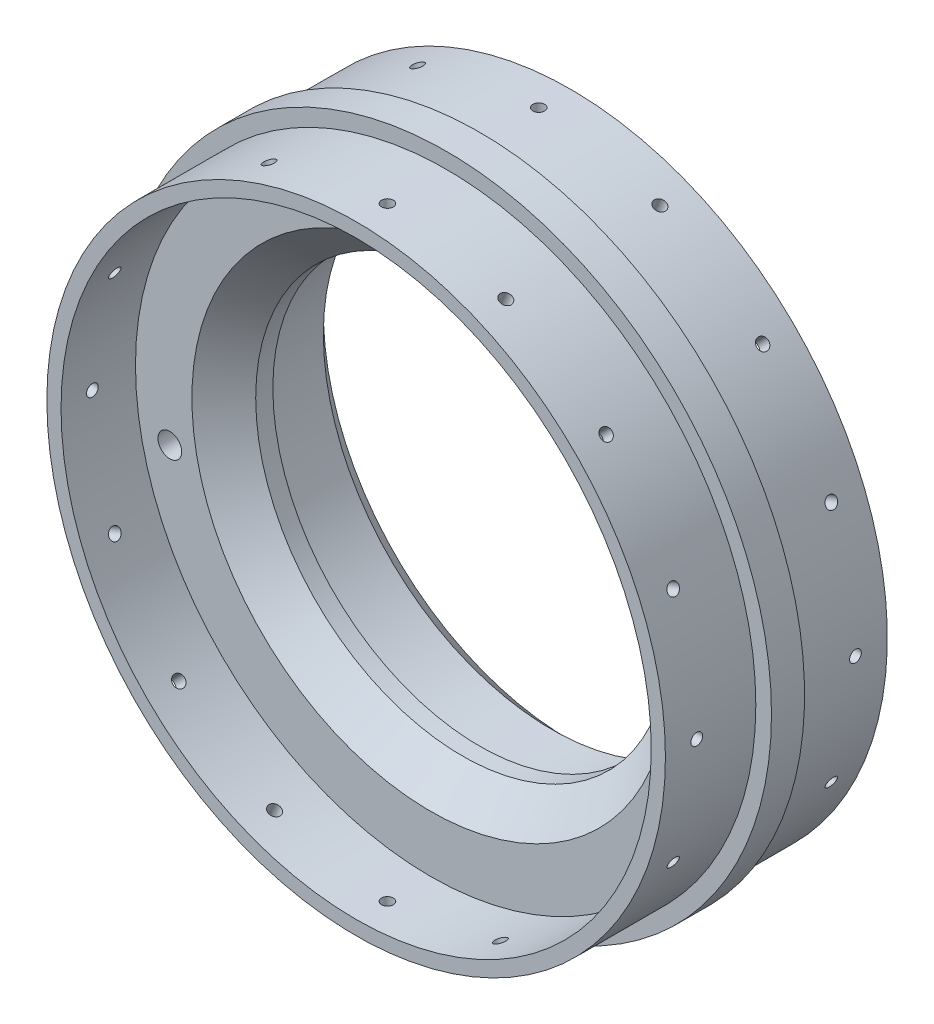
SolidWorks part; units mm, degrees
material "6061-T6 (SS)"
ref_plane "Front Plane" through (0, 0, 0) normal (0, 0, 1) x (1, 0, 0)
ref_plane "Top Plane" through (0, 0, 0) normal (0, 1, 0) x (1, 0, 0)
ref_plane "Right Plane" through (0, 0, 0) normal (1, 0, 0) x (0, 0, -1)
sketch "Sketch5" plane through (0, 0, 0) normal (0, 0, 1) x (1, 0, 0)
  circle A0 centre (0, 0) radius 69.85
extrude "Extrude1" add sketch "Sketch5" along normal blind 46.101
sketch "Sketch8" plane through (0, 0, 46.101) normal (0, 0, 1) x (1, 0, 0)
  circle A0 centre (0, 0) radius 44.45
extrude "Extrude4" cut sketch "Sketch8" against normal through all
sketch "Sketch6" plane through (0, 0, 46.101) normal (0, 0, 1) x (1, 0, 0)
  circle A0 centre (0, 0) radius 66.4845
extrude "Extrude2" cut sketch "Sketch6" against normal blind 19.431 flip side to cut
sketch "Sketch7" plane through (0, 0, 46.101) normal (0, 0, 1) x (1, 0, 0)
  circle A0 centre (0, 0) radius 63.4365
extrude "Extrude3" cut sketch "Sketch7" against normal blind 16.002
chamfer "Chamfer1" distance 6.858 distance2 6.858 1 edges at (44.45, 0, 30.099)
sketch "Sketch9" plane through (0, 0, 0) normal (0, 0, -1) x (-1, 0, 0)
  circle A0 centre (0, 0) radius 68.0847
extrude "Extrude5" cut sketch "Sketch9" against normal blind 19.558 flip side to cut
sketch "Sketch10" plane through (0, 0, 0) normal (0, 0, -1) x (-1, 0, 0)
  circle A0 centre (0, 0) radius 65.0367
  circle A1 centre (0, 0) radius 53.7845
extrude "Extrude6" cut sketch "Sketch10" against normal blind 9.525
sketch "Sketch11" plane through (0, 0, 0) normal (0, 0, -1) x (-1, 0, 0)
  circle A0 centre (0, 0) radius 49.0855
extrude "Extrude7" cut sketch "Sketch11" against normal blind 19.558
chamfer "Chamfer2" distance 4.064 angle 45 1 edges at (-49.0855, 0, 0)
ref_plane "Plane1" through (0, 0, 39.37) normal (0, 0, 1) x (1, 0, 0)
ref_plane "Plane2" through (0, 0, 6.858) normal (0, 0, -1) x (-1, 0, 0)
sketch "Sketch13" plane through (0, 0, 6.858) normal (0, 0, -1) x (-1, 0, 0)
  line L0 (0, 0) -> (0, 68.0847) construction
  circle A0 centre (0, 0) radius 68.0847 construction
ref_plane "Plane3" through (0, 68.0847, 6.858) normal (0, 1, 0) x (-1, 0, 0)
sketch "Sketch15" plane through (0, 0, 39.37) normal (0, 0, 1) x (1, 0, 0)
  line L0 (0, 0) -> (0, 66.4845) construction
  line L1 (0, 0) -> (0, 68.0847) construction
  circle A0 centre (0, 0) radius 66.4845 construction
ref_plane "Plane4" through (0, 66.4845, 39.37) normal (0, 1, 0) x (-1, 0, 0)
hole_wizard "#39 (0.0995) Diameter Hole2" positions "Sketch20" profile "Sketch19" hole size "#39" standard "Ansi Inch"
sketch "Sketch20" plane through (0, 68.0847, 6.858) normal (0, 1, 0) x (-1, 0, 0)
  point P1 (0, 0)
sketch "Sketch19" plane through (0, 68.0847, 6.858) normal (1, 0, 0) x (0, 0, 1)
  line L0 (0, 0) -> (0, 13.4593)
  line L1 (0, 13.4593) -> (1.2636, 12.7)
  line L2 (1.2636, 12.7) -> (1.2636, 0)
  line L5 (1.2636, 0) -> (0, 0)
  line L10 (0, 13.4593) -> (-1.2636, 12.7) construction
  line L11 (0, -6.35) -> (0, 107.95) construction
  dimension "Hole Dia." = 2.5273
  dimension "Hole Depth" = 12.7
  dimension "Drill Angle" = 118
hole_wizard "#39 (0.0995) Diameter Hole6" positions "Sketch26" profile "Sketch25" hole size "#39" standard "Ansi Inch"
sketch "Sketch26" plane through (0, 66.4845, 39.37) normal (0, 1, 0) x (-1, 0, 0)
  point P1 (0, 0)
sketch "Sketch25" plane through (0, 66.4845, 39.37) normal (1, 0, 0) x (0, 0, 1)
  line L0 (0, 0) -> (0, 13.4593)
  line L1 (0, 13.4593) -> (1.2636, 12.7)
  line L2 (1.2636, 12.7) -> (1.2636, 0)
  line L5 (1.2636, 0) -> (0, 0)
  line L10 (0, 13.4593) -> (-1.2636, 12.7) construction
  line L11 (0, -6.35) -> (0, 107.95) construction
  dimension "Hole Dia." = 2.5273
  dimension "Hole Depth" = 12.7
  dimension "Drill Angle" = 118
pattern_circular "CirPattern1" count 16 over 360 about axis through (0, 0, 19.558) along (0, 0, -1) of "#39 (0.0995) Diameter Hole2", "#39 (0.0995) Diameter Hole6"
ref_plane "Plane5" through (0, 0, 23.114) normal (0, 0, 1) x (1, 0, 0)
sketch "Sketch27" plane through (0, 0, 23.114) normal (0, 0, 1) x (1, 0, 0)
  line L0 (0, -65.0367) -> (0, -68.0847) construction
  arc A0 (0, -69.85) -> (13.6271, -68.5079) centre (0, 0) ccw construction
  circle A1 centre (0, 0) radius 69.85 construction
ref_plane "Plane6" through (13.6271, -68.5079, 23.114) normal (0.1951, -0.9808, 0) x (0.9808, 0.1951, 0)
hole_wizard "#21 (0.159) Diameter Hole1" positions "Sketch29" profile "Sketch28" hole size "#21" standard "Ansi Inch"
sketch "Sketch29" plane through (13.6271, -68.5079, 23.114) normal (0.1951, -0.9808, 0) x (0.9808, 0.1951, 0)
  point P1 (0, 0)
sketch "Sketch28" plane through (13.6271, -68.5079, 23.114) normal (0, 0, 1) x (0.9808, 0.1951, 0)
  line L0 (0, 0) -> (0, 13.9133)
  line L1 (0, 13.9133) -> (2.0193, 12.7)
  line L2 (2.0193, 12.7) -> (2.0193, 0)
  line L5 (2.0193, 0) -> (0, 0)
  line L10 (0, 13.9133) -> (-2.0193, 12.7) construction
  line L11 (0, -6.35) -> (0, 107.95) construction
  dimension "Hole Dia." = 4.0386
  dimension "Hole Depth" = 12.7
  dimension "Drill Angle" = 118
sketch "Sketch30" plane through (0, 0, 30.099) normal (0, 0, 1) x (1, 0, 0)
  arc A0 (0, -57.15) -> (56.0519, 11.1494) centre (0, 0) ccw construction
hole_wizard "#7 (0.201) Diameter Hole1" positions "3DSketch1" profile "Sketch31" hole size "#7" standard "Ansi Inch" end condition through all
sketch3d "3DSketch1"
  point P0 (56.0519, 11.1494, 30.099)
sketch "Sketch31" plane through (56.0519, 11.1494, 30.099) normal (1, 0, 0) x (0, -1, 0)
  line L0 (0, 0) -> (0, 30.099)
  line L1 (0, 30.099) -> (2.5527, 30.099)
  line L2 (2.5527, 30.099) -> (2.5527, 0)
  line L5 (2.5527, 0) -> (0, 0)
  line L11 (0, -6.35) -> (0, 107.95) construction
  dimension "Thru Hole Dia." = 5.1054
  dimension "Thru Hole Depth" = 30.099
pattern_circular "CirPattern2" count 2 over 360 about axis through (0, 0, 26.67) along (0, 0, 1) of "#7 (0.201) Diameter Hole1"
